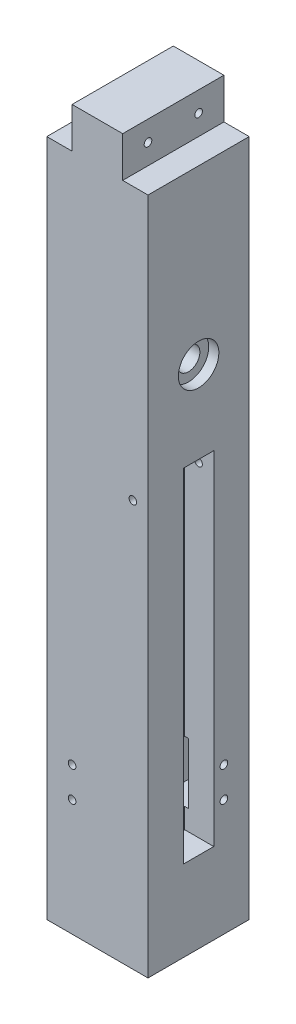
SolidWorks part; units mm, degrees
material "Pine"
ref_plane "Front Plane" through (0, 0, 0) normal (0, 0, 1) x (1, 0, 0)
ref_plane "Top Plane" through (0, 0, 0) normal (0, 1, 0) x (1, 0, 0)
ref_plane "Right Plane" through (0, 0, 0) normal (1, 0, 0) x (0, 0, -1)
sketch "Sketch1" plane through (0, 0, 0) normal (0, 0, 1) x (1, 0, 0)
  line L1 (63.5, 425.45) -> (-63.5, 425.45)
  line L2 (63.5, 425.45) -> (63.5, -425.45)
  line L3 (63.5, -425.45) -> (-63.5, -425.45)
  line L4 (-63.5, 425.45) -> (-63.5, -425.45)
  line L5 (63.5, 425.45) -> (-63.5, -425.45) construction
  line L6 (63.5, -425.45) -> (-63.5, 425.45) construction
  line L7 (31.75, 476.25) -> (-31.75, 476.25)
  line L8 (31.75, 476.25) -> (31.75, 374.65)
  line L9 (31.75, 374.65) -> (-31.75, 374.65)
  line L10 (-31.75, 476.25) -> (-31.75, 374.65)
  line L11 (31.75, 476.25) -> (-31.75, 374.65) construction
  line L12 (31.75, 374.65) -> (-31.75, 476.25) construction
  point P0 (0, 0)
  point P6 (0, 425.45)
  dimension "D1" = 850.9
  dimension "D2" = 101.6
  dimension "D3" = 63.5
  dimension "D4" = 127
extrude "Boss-Extrude1" add sketch "Sketch1" along normal blind 127 contours L10 L1 L4 L3 L2 L8 L9 | L1 L10 L9 L8 | L7 L10 L1 L8 region at (0, -12.3092, 0) region at (0, 400.05, 0) region at (0, 450.85, 0)
sketch "Sketch2" plane through (63.5, 0, 0) normal (1, 0, 0) x (0, 0, -1)
  line L0 (-63.5, -381) -> (-63.5, 49619) construction
  line L1 (-127, -425.45) -> (0, -425.45) construction
  line L2 (-127, 450.85) -> (0, 450.85) construction
  line L3 (-57.15, -527.05) -> (-69.85, -527.05)
  line L4 (-57.15, -527.05) -> (-57.15, -323.85)
  line L5 (-57.15, -323.85) -> (-69.85, -323.85)
  line L6 (-69.85, -527.05) -> (-69.85, -323.85)
  line L7 (-57.15, -527.05) -> (-69.85, -323.85) construction
  line L8 (-57.15, -323.85) -> (-69.85, -527.05) construction
  line L9 (-127, 476.25) -> (-127, 425.45) construction
  line L10 (0, 476.25) -> (0, 425.45) construction
  circle A0 centre (-63.5, 209.55) radius 25.4
  circle A1 centre (-63.5, 209.55) radius 14.2875
  circle A2 centre (-95.25, 450.85) radius 4.7625
  circle A3 centre (-31.75, 450.85) radius 4.7625
  point P4 (-63.5, -425.45)
  point P5 (-63.5, -425.45)
  dimension "D3" = 50.8
  dimension "D4" = 28.575
  dimension "D5" = 635
  dimension "D6" = 9.525
  dimension "D7" = 31.75
  dimension "D8" = 31.75
  dimension "D1" = 203.2
  dimension "D2" = 12.7
extrude "Cut-Extrude1" cut sketch "Sketch2" against normal through all contours A2 | A3 | A1 region at (63.5, 209.55, 63.5) region at (63.5, 450.85, 95.25) region at (63.5, 450.85, 31.75)
sketch "Sketch3" plane through (0, 0, 0) normal (0, 0, -1) x (-1, 0, 0)
  line L0 (-63.5, 425.45) -> (-63.5, -425.45) construction
  line L1 (0, -222.25) -> (-31.75, -222.25)
  line L2 (0, -222.25) -> (0, -298.45)
  line L3 (0, -298.45) -> (-31.75, -298.45)
  line L4 (-31.75, -222.25) -> (-31.75, -298.45)
  line L5 (0, -222.25) -> (-31.75, -298.45) construction
  line L6 (0, -298.45) -> (-31.75, -222.25) construction
  line L7 (-63.5, -425.45) -> (63.5, -425.45) construction
  point P0 (-15.875, -260.35)
  dimension "D1" = 76.2
  dimension "D2" = 31.75
  dimension "D3" = 31.75
  dimension "D4" = 127
extrude "Cut-Extrude2" cut sketch "Sketch3" against normal blind 63.5
extrude "Cut-Extrude3" cut sketch "Sketch2<3>" against normal blind 12.7 contours A0 A1 region at (63.5, 209.55, 88.1816)
sketch "Sketch2<3>" plane through (63.5, 0, 0) normal (1, 0, 0) x (0, 0, -1) same geometry as "Sketch2"
sketch "Sketch4" plane through (63.5, 0, 0) normal (1, 0, 0) x (0, 0, -1)
  line L0 (-31.75, -222.25) -> (-31.75, -298.45) construction
  line L4 (0, -298.45) -> (0, -222.25)
  line L5 (-63.5, -298.45) -> (0, -298.45)
  line L6 (-63.5, -222.25) -> (-63.5, -298.45)
  line L7 (0, -222.25) -> (-63.5, -222.25)
  line L8 (0, -298.45) -> (0, -222.25)
  line L9 (-63.5, -298.45) -> (0, -298.45)
  line L10 (-63.5, -222.25) -> (-63.5, -298.45)
  line L11 (0, -222.25) -> (-63.5, -222.25)
  circle A0 centre (-31.75, -279.4) radius 4.7625
  circle A1 centre (-31.75, -241.3) radius 4.7625
  point P10 (-31.75, -260.35)
  dimension "D2" = 19.05
  dimension "D3" = 19.05
  dimension "D4" = 9.525
  dimension "D5" = 31.75
  dimension "D1" = 0
extrude "Cut-Extrude4" cut sketch "Sketch4" against normal blind 69.85 contours A0 L0 | L0 A0 | A1 L0 | L0 A1 region at (63.5, -241.3, 29.7287) region at (63.5, -241.3, 33.7713) region at (63.5, -279.4, 29.7287) region at (63.5, -279.4, 33.7713)
sketch "Sketch5" plane through (-63.5, 0, 0) normal (-1, 0, 0) x (0, 0, 1)
  line L0 (127, 425.45) -> (127, -425.45) construction
  line L1 (95.25, -222.25) -> (63.5, -222.25)
  line L2 (95.25, -222.25) -> (95.25, -298.45)
  line L3 (95.25, -298.45) -> (63.5, -298.45)
  line L4 (63.5, -222.25) -> (63.5, -298.45)
  line L5 (95.25, -222.25) -> (63.5, -298.45) construction
  line L6 (95.25, -298.45) -> (63.5, -222.25) construction
  line L7 (127, -425.45) -> (0, -425.45) construction
  point P0 (79.375, -260.35)
  dimension "D1" = 76.2
  dimension "D2" = 31.75
  dimension "D3" = 31.75
  dimension "D4" = 127
extrude "Cut-Extrude6" cut sketch "Sketch5" against normal blind 63.246
sketch "Sketch6" plane through (0, 0, 127) normal (0, 0, 1) x (1, 0, 0)
  line L0 (-31.75, -222.25) -> (-31.75, -298.45) construction
  line L4 (-63.5, -222.25) -> (-63.5, -298.45)
  line L5 (-0.254, -222.25) -> (-63.5, -222.25)
  line L6 (-0.254, -298.45) -> (-0.254, -222.25)
  line L7 (-63.5, -298.45) -> (-0.254, -298.45)
  line L8 (-63.5, -222.25) -> (-63.5, -298.45)
  line L9 (-0.254, -222.25) -> (-63.5, -222.25)
  line L10 (-0.254, -298.45) -> (-0.254, -222.25)
  line L11 (-63.5, -298.45) -> (-0.254, -298.45)
  circle A0 centre (-31.75, -279.4) radius 4.7625
  circle A1 centre (-31.75, -241.3) radius 4.7625
  point P10 (-31.75, -260.35)
  dimension "D2" = 9.525
  dimension "D4" = 19.05
  dimension "D3" = 19.05
  dimension "D5" = 31.75
  dimension "D1" = 0
extrude "Cut-Extrude7" cut sketch "Sketch6" against normal blind 69.85 contours A0 L0 | L0 A0 | L0 A1 | A1 L0 region at (-29.7287, -241.3, 127) region at (-33.7713, -241.3, 127) region at (-29.7287, -279.4, 127) region at (-33.7713, -279.4, 127)
sketch "Sketch7" plane through (63.5, 0, 0) normal (1, 0, 0) x (0, 0, -1)
  line L4 (-82.55, 106.3625) -> (-82.55, -323.85)
  line L5 (-44.45, 106.3625) -> (-82.55, 106.3625)
  line L6 (-44.45, -323.85) -> (-44.45, 106.3625)
  line L7 (-82.55, -323.85) -> (-44.45, -323.85)
  line L8 (-82.55, 106.3625) -> (-82.55, -323.85)
  line L9 (-44.45, 106.3625) -> (-82.55, 106.3625)
  line L10 (-44.45, -323.85) -> (-44.45, 106.3625)
  line L11 (-82.55, -323.85) -> (-44.45, -323.85)
  dimension "D1" = 0
extrude "Cut-Extrude8" cut sketch "Sketch7" against normal blind 36.5125
sketch "Sketch8" plane through (0, 0, 0) normal (0, 0, -1) x (-1, 0, 0)
  line L0 (-44.45, 106.3625) -> (-44.45, -323.85) construction
  line L8 (-31.75, -298.45) -> (-31.75, -222.25)
  line L9 (-26.9875, -298.45) -> (-31.75, -298.45)
  line L10 (-26.9875, -323.85) -> (-26.9875, -298.45)
  line L11 (-63.5, -323.85) -> (-26.9875, -323.85)
  line L12 (-63.5, 106.3625) -> (-63.5, -323.85)
  line L13 (-26.9875, 106.3625) -> (-63.5, 106.3625)
  line L14 (-26.9875, -222.25) -> (-26.9875, 106.3625)
  line L15 (-31.75, -222.25) -> (-26.9875, -222.25)
  line L16 (-31.75, -298.45) -> (-31.75, -222.25)
  line L17 (-26.9875, -298.45) -> (-31.75, -298.45)
  line L18 (-26.9875, -323.85) -> (-26.9875, -298.45)
  line L19 (-63.5, -323.85) -> (-26.9875, -323.85)
  line L20 (-63.5, 106.3625) -> (-63.5, -323.85)
  line L21 (-26.9875, 106.3625) -> (-63.5, 106.3625)
  line L22 (-26.9875, -222.25) -> (-26.9875, 106.3625)
  line L23 (-31.75, -222.25) -> (-26.9875, -222.25)
  circle A0 centre (-44.45, 84.1375) radius 4.7625
  dimension "D4" = 9.525
  dimension "D2" = 19.05
  dimension "D3" = 22.225
  dimension "D1" = 0
extrude "Cut-Extrude9" cut sketch "Sketch8" against normal through all contours A0 L0 | L0 A0 region at (42.4287, 84.1375, 0) region at (46.4713, 84.1375, 0)
